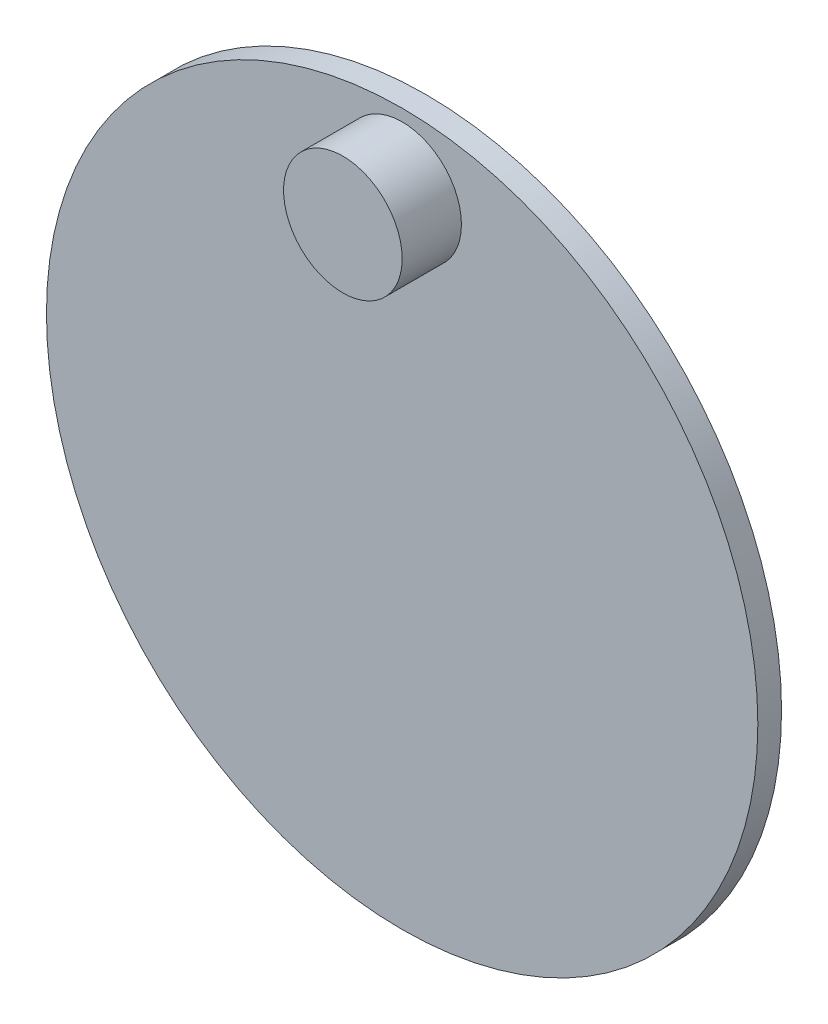
SolidWorks part; units mm, degrees
ref_plane "Front Plane" through (0, 0, 0) normal (0, 0, 1) x (1, 0, 0)
ref_plane "Top Plane" through (0, 0, 0) normal (0, 1, 0) x (1, 0, 0)
ref_plane "Right Plane" through (0, 0, 0) normal (1, 0, 0) x (0, 0, -1)
sketch "Sketch1" plane through (0, 0, 0) normal (0, 0, 1) x (1, 0, 0)
  circle A0 centre (0, 0) radius 38.1
  dimension "D1" = 76.2
extrude "Boss-Extrude1" add sketch "Sketch1" along normal blind 2.54
sketch "Sketch2" plane through (0, 0, 2.54) normal (0, 0, 1) x (1, 0, 0)
  line L0 (0, 38.1) -> (0, -38.1) construction
  circle A0 centre (0, 0) radius 38.1 construction
  circle A1 centre (0, 30.48) radius 6.35
  dimension "D1" = 12.7
  dimension "D2" = 30.48
extrude "Boss-Extrude2" add sketch "Sketch2" along normal blind 6.35
sketch "Sketch3" plane through (0, 0, 0) normal (0, 0, -1) x (-1, 0, 0)
  circle A0 centre (0, 0) radius 6.35
  dimension "D1" = 12.7
extrude "Boss-Extrude3" add sketch "Sketch3" along normal blind 19.05
